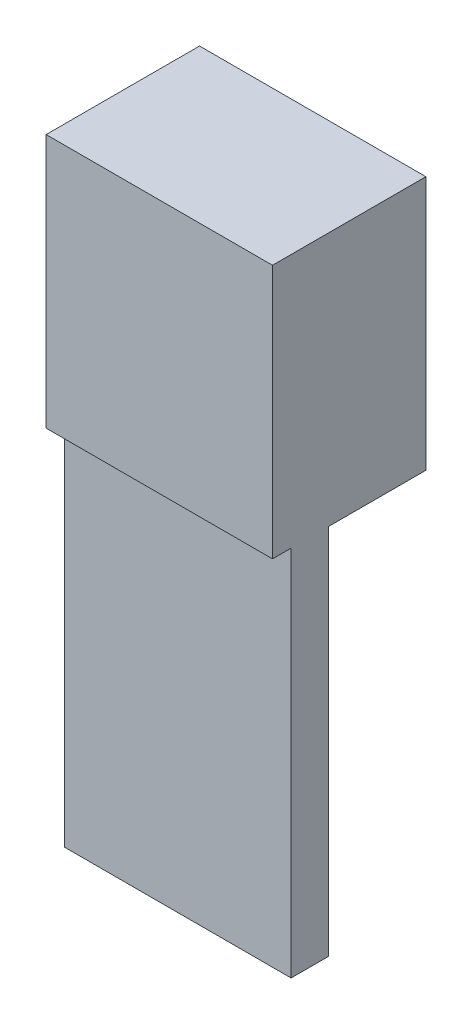
SolidWorks part; units mm, degrees
ref_plane "前视基准面" through (0, 0, 0) normal (0, 0, 1) x (1, 0, 0)
ref_plane "上视基准面" through (0, 0, 0) normal (0, 1, 0) x (1, 0, 0)
ref_plane "右视基准面" through (0, 0, 0) normal (1, 0, 0) x (0, 0, -1)
sketch "草图1" plane through (0, 0, 0) normal (0, 0, 1) x (1, 0, 0)
  line L0 (-3.04, 0) -> (3.04, 0) construction
  line L1 (-3.04, 3.415) -> (3.04, 3.415)
  line L2 (-3.04, 3.415) -> (-3.04, -3.415)
  line L3 (-3.04, -3.415) -> (3.04, -3.415)
  line L4 (3.04, 3.415) -> (3.04, -3.415)
  dimension "D1" = 6.08
  dimension "D2" = 6.83
extrude "拉伸1" add sketch "草图1" along normal blind 4.12
sketch "草图2" plane through (0, 0, 0) normal (0, 0, -1) x (-1, 0, 0)
  line L0 (-3.04, 3.415) -> (3.04, 3.415) construction
  line L1 (0, 0) -> (0, 0.565) construction
  circle A0 centre (0, 0.565) radius 2.35
  dimension "D1" = 4.7
  dimension "D2" = 2.85
extrude "拉伸2" add sketch "草图2" along normal blind 0.1
dome "圆顶1" faces to dome 1 distance 1.45 reverse direction no elliptical dome no face at (-2.35, 0.565, -0.1) parameters "D1"=1.45
sketch "草图3" plane through (3.04, 0, 0) normal (1, 0, 0) x (0, 0, -1)
  line L0 (1.55, 0.565) -> (1.55, -2.9803)
  line L1 (-4.12, -3.415) -> (-4.12, 3.415) construction
  arc A0 (0.1, -1.785) -> (0.1, 2.915) centre (-1.0793, 0.565) ccw construction
  arc A1 (0.1, -1.785) -> (0.1, 2.915) centre (-1.0793, 0.565) ccw
  dimension "D1" = 5.67
sketch "草图4" plane through (0, -3.415, 0) normal (0, -1, 0) x (1, 0, 0)
  line L0 (3.04, 4.12) -> (3.04, 0) construction
  line L1 (3.04, 3.62) -> (-3.04, 3.62)
  line L2 (3.04, 3.62) -> (3.04, 2.62)
  line L3 (3.04, 2.62) -> (-3.04, 2.62)
  line L4 (-3.04, 3.62) -> (-3.04, 2.62)
  line L5 (-3.04, 4.12) -> (-3.04, 0) construction
  line L6 (-3.04, 4.12) -> (3.04, 4.12) construction
  dimension "D1" = 1
  dimension "D2" = 0.5
extrude "凸台-拉伸1" add sketch "草图4" along normal blind 10
